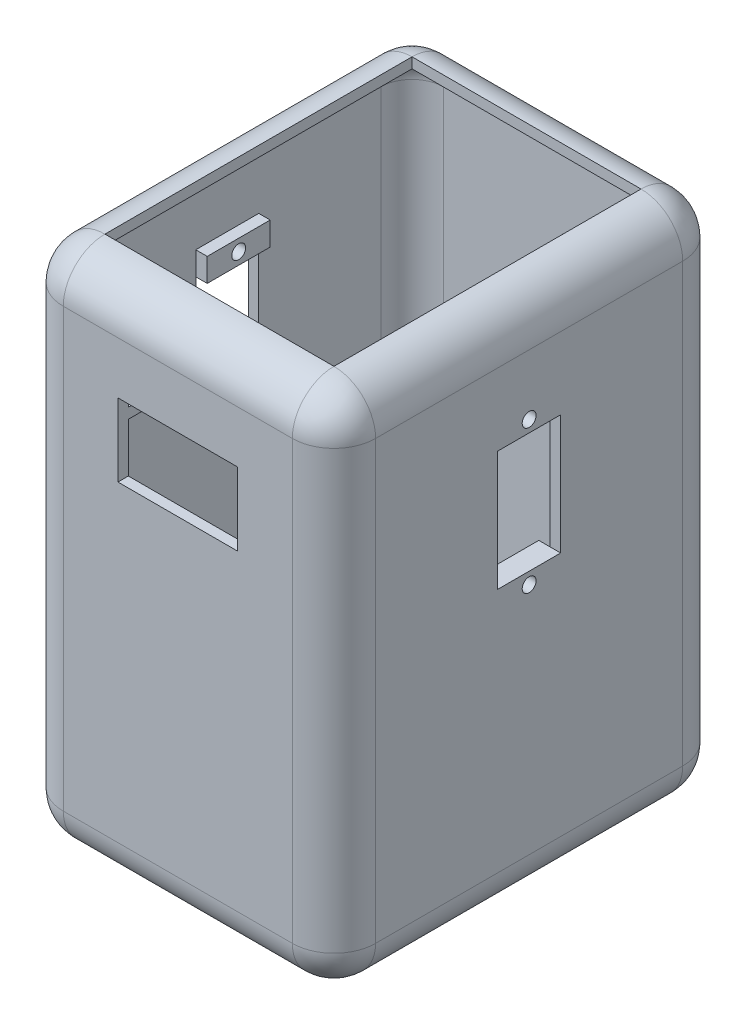
SolidWorks part; units mm, degrees
ref_plane "Front Plane" through (0, 0, 0) normal (0, 0, 1) x (1, 0, 0)
ref_plane "Top Plane" through (0, 0, 0) normal (0, 1, 0) x (1, 0, 0)
ref_plane "Right Plane" through (0, 0, 0) normal (1, 0, 0) x (0, 0, -1)
sketch "Sketch2" plane through (0, 0, 0) normal (0, 1, 0) x (1, 0, 0)
  line L1 (-30, 37.5) -> (30, 37.5)
  line L2 (-30, 37.5) -> (-30, -37.5)
  line L3 (-30, -37.5) -> (30, -37.5)
  line L4 (30, 37.5) -> (30, -37.5)
  line L5 (-30, 37.5) -> (30, -37.5) construction
  line L6 (-30, -37.5) -> (30, 37.5) construction
  point P0 (0, 0)
  dimension "D1" = 75
  dimension "D2" = 60
extrude "Boss-Extrude2" add sketch "Sketch2" along normal blind 100
fillet "Fillet1" radius 8 12 edges at (0, 0, -37.5) (30, 50, -37.5) (30, 0, 0) (30, 50, 37.5) (0, 0, 37.5) (0, 100, 37.5) (0, 100, -37.5) (30, 100, 0) (-30, 50, -37.5) (-30, 100, 0) (-30, 50, 37.5) (-30, 0, 0)
shell "Shell1" thickness 2 removed face at (0, 100, 0)
sketch "Sketch3" plane through (0, 0, 37.5) normal (0, 0, 1) x (1, 0, 0)
  line L1 (11.5, 82) -> (-11.5, 82)
  line L2 (11.5, 82) -> (11.5, 68)
  line L3 (11.5, 68) -> (-11.5, 68)
  line L4 (-11.5, 82) -> (-11.5, 68)
  line L5 (11.5, 82) -> (-11.5, 68) construction
  line L6 (11.5, 68) -> (-11.5, 82) construction
  line L7 (-22, 100) -> (22, 100) construction
  point P0 (0, 75)
  point P5 (0, 0)
  point P6 (0, 0)
  dimension "D1" = 23
  dimension "D2" = 14
  dimension "D3" = 25
extrude "Cut-Extrude1" cut sketch "Sketch3" against normal up to next
sketch "Sketch4" plane through (0, 0, -37.5) normal (0, 0, -1) x (-1, 0, 0)
  line L0 (-30, 2) -> (30, 2) construction
  line L3 (-30, 0) -> (30, 0) construction
  circle A0 centre (0, 7.5) radius 5.5
  point P4 (0, 0)
  point P10 (0, 0)
  point P12 (0, 0)
  dimension "D1" = 11
  dimension "D2" = 2
extrude "Cut-Extrude2" cut sketch "Sketch4" against normal up to next
sketch "Sketch5" plane through (30, 0, 0) normal (1, 0, 0) x (0, 0, -1)
  line L0 (-37.5, 66.67) -> (37.5, 66.67) construction
  line L4 (-29.5, 100) -> (29.5, 100) construction
  line L5 (-6.05, 78.17) -> (6.05, 78.17)
  line L6 (-6.05, 78.17) -> (-6.05, 55.17)
  line L7 (-6.05, 55.17) -> (6.05, 55.17)
  line L8 (6.05, 78.17) -> (6.05, 55.17)
  line L9 (-6.05, 78.17) -> (6.05, 55.17) construction
  line L10 (-6.05, 55.17) -> (6.05, 78.17) construction
  circle A0 centre (0, 66.67) radius 17.5 construction
  point P7 (0, 0)
  point P11 (0, 0)
  dimension "D1" = 35
  dimension "D2" = 33.33
  dimension "D3" = 12.1
  dimension "D4" = 23
extrude "Cut-Extrude3" cut sketch "Sketch5" against normal through all
sketch "Sketch6" plane through (28, 0, 0) normal (-1, 0, 0) x (0, 0, 1)
  line L0 (6.05, 55.17) -> (6.05, 78.17) construction
  line L1 (-6.05, 55.17) -> (6.05, 55.17)
  line L2 (-6.05, 55.17) -> (-6.05, 50.67)
  line L3 (-6.05, 50.67) -> (6.05, 50.67)
  line L4 (6.05, 55.17) -> (6.05, 50.67)
  line L5 (-6.05, 66.67) -> (6.05, 66.67) construction
  line L6 (-6.05, 78.17) -> (-6.05, 55.17) construction
  line L7 (6.05, 78.17) -> (6.05, 82.67)
  line L8 (-6.05, 82.67) -> (6.05, 82.67)
  line L9 (-6.05, 78.17) -> (-6.05, 82.67)
  line L10 (-6.05, 78.17) -> (6.05, 78.17)
  point P10 (-6.05, 52.92)
  point P13 (0, 50.67)
  dimension "D1" = 4.5
extrude "Boss-Extrude3" add sketch "Sketch6" along normal blind 2.2
sketch "Sketch7" plane through (25.8, 0, 0) normal (-1, 0, 0) x (0, 0, 1)
  line L0 (-6.05, 55.17) -> (6.05, 50.67) construction
  line L1 (-6.05, 66.67) -> (6.05, 66.67) construction
  line L2 (-6.05, 78.17) -> (-6.05, 55.17) construction
  line L3 (6.05, 55.17) -> (6.05, 78.17) construction
  circle A0 centre (0, 52.92) radius 1.335
  circle A1 centre (0, 80.42) radius 1.335
  point P7 (0, 52.92)
  dimension "D1" = 2.67
extrude "Cut-Extrude4" cut sketch "Sketch7" against normal through all
mirror "Mirror1" about plane through (0, 0, 0) normal (1, 0, 0) of "Cut-Extrude4", "Boss-Extrude3"
ref_plane "Plane2" through (0, 79.45, 0) normal (0, -1, 0) x (-1, 0, 0)
sketch "Sketch12" plane through (0, 79.45, 0) normal (0, -1, 0) x (-1, 0, 0)
  line L0 (-11.5, -35.5) -> (-11.5, -32.5)
  line L1 (-22, -35.5) -> (22, -35.5) construction
  line L2 (-11.5, -35.5) -> (11.5, -35.5) construction
  line L3 (-11.5, -32.5) -> (11.5, -32.5)
  line L4 (11.5, -32.5) -> (11.5, -35.5)
  line L5 (-13.5, -35.5) -> (-13.5, -30.5)
  line L6 (-13.5, -30.5) -> (13.5, -30.5)
  line L7 (13.5, -30.5) -> (13.5, -35.5)
  line L8 (-11.5, -35.5) -> (-11.5, -37.5) construction
  line L9 (11.5, -35.5) -> (11.5, -37.5) construction
  line L10 (13.5, -35.5) -> (11.5, -35.5)
  line L11 (-11.5, -35.5) -> (-13.5, -35.5)
  dimension "D1" = 2
  dimension "D2" = 2
  dimension "D3" = 2
  dimension "D4" = 3
extrude "Boss-Extrude4" add sketch "Sketch12" along normal blind 2
ref_plane "Plane3" through (0, 0, -15.5) normal (0, 0, 1) x (1, 0, 0)
sketch "Sketch14" plane through (0, 0, -15.5) normal (0, 0, 1) x (1, 0, 0)
  line L0 (22, 2) -> (-22, 2) construction
  line L1 (7, 2) -> (-7, 2)
  line L2 (7, 2) -> (7, 4)
  line L3 (7, 4) -> (-7, 4)
  line L4 (-7, 2) -> (-7, 4)
  point P6 (0, 4)
  dimension "D1" = 2
  dimension "D2" = 14
extrude "Boss-Extrude6" add sketch "Sketch14" against normal blind 14
sketch "Sketch15" plane through (-30, 0, 0) normal (-1, 0, 0) x (0, 0, 1)
  line L0 (0, 55.17) -> (0, 0) construction
  line L1 (6.05, 55.17) -> (-6.05, 55.17) construction
  line L2 (3.05, 22.5) -> (-3.05, 22.5)
  line L3 (3.05, 20) -> (-3.05, 20)
  line L4 (4.3, 27.7181) -> (4.3, 12.5631) construction
  line L5 (-29.5, 8) -> (29.5, 8) construction
  circle A0 centre (3.05, 21.25) radius 1.25
  circle A1 centre (-3.05, 21.25) radius 1.25
  point P6 (4.1, 12.5631)
  point P13 (2.85, 41.8012)
  point P14 (2.85, 19.618)
  point P18 (0, 20)
  point P21 (0, 22.5)
  point P22 (4.1, 27.7181)
  point P23 (0, 0)
  dimension "D1" = 2.5
  dimension "D2" = 4.3
  dimension "D3" = 12
extrude "Cut-Extrude5" cut sketch "Sketch15" against normal up to next contours L2 A1 L3 A0 | A1 | A0 region at (-30, 21.25, 0) region at (-30, 21.25, 3.05) region at (-30, 21.25, -3.05)
sketch "Sketch16" plane through (-28, 0, 0) normal (1, 0, 0) x (0, 0, -1)
  line L0 (0, 22.5) -> (0, 20) construction
  line L1 (-5, 20) -> (5, 20)
  line L2 (-5, 20) -> (-5, 18)
  line L3 (-5, 18) -> (5, 18)
  line L4 (5, 20) -> (5, 18)
  line L5 (-3.05, 22.5) -> (3.05, 22.5) construction
  line L6 (-3.05, 20) -> (3.05, 20) construction
  point P10 (0, 18)
  dimension "D1" = 2
  dimension "D2" = 10
extrude "Boss-Extrude7" add sketch "Sketch16" along normal blind 21
